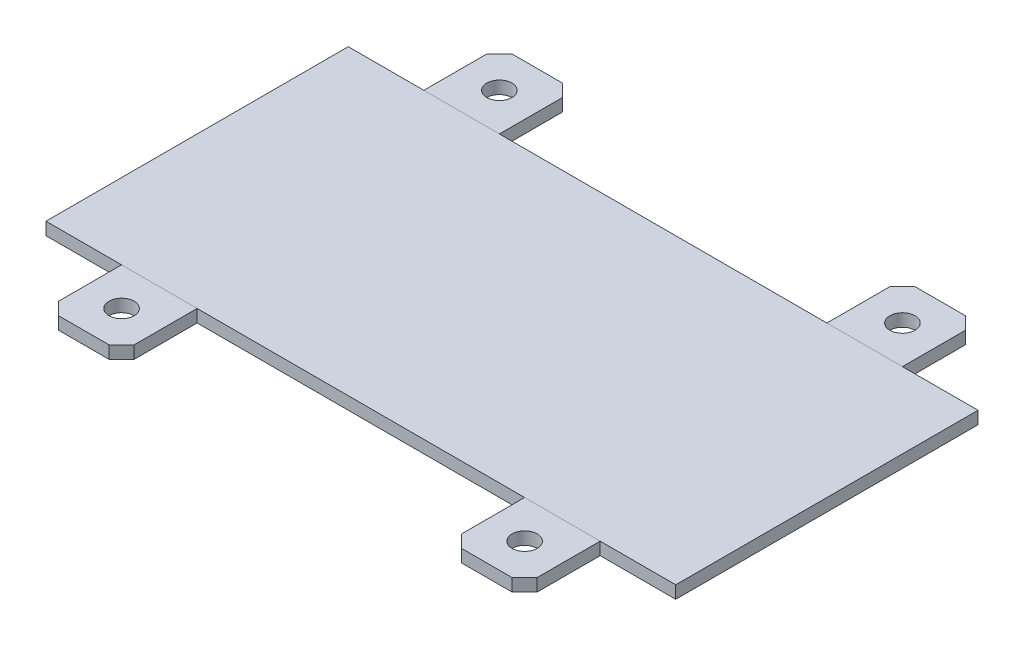
SolidWorks part; units mm, degrees
material "Сталь 3 ГОСТ 535-88"
ref_plane "Спереди" through (0, 0, 0) normal (0, 0, 1) x (1, 0, 0)
ref_plane "Сверху" through (0, 0, 0) normal (0, 1, 0) x (1, 0, 0)
ref_plane "Справа" through (0, 0, 0) normal (1, 0, 0) x (0, 0, -1)
sketch "Эскиз1" plane through (0, 0, 0) normal (0, 1, 0) x (1, 0, 0)
  line L1 (-125, 60) -> (125, 60)
  line L2 (-125, 60) -> (-125, -60)
  line L3 (-125, -60) -> (125, -60)
  line L4 (125, 60) -> (125, -60)
  line L5 (0, -60) -> (0, 60) construction
  line L6 (-125, 0) -> (125, 0) construction
  point P0 (0, 0)
  dimension "D1" = 120
  dimension "D2" = 250
extrude "Бобышка-Вытянуть1" add sketch "Эскиз1" along normal blind 5
sketch "Эскиз2" plane through (0, 0, 0) normal (0, 1, 0) x (1, 0, 0)
  line L0 (125, 60) -> (-125, 60) construction
  line L1 (-95, 60) -> (-65, 60)
  line L2 (-95, 60) -> (-95, 90)
  line L3 (-95, 90) -> (-65, 90)
  line L4 (-65, 60) -> (-65, 90)
  line L5 (-125, 60) -> (-125, -60) construction
  line L6 (-80, 90) -> (-80, 60) construction
  circle A0 centre (-80, 75) radius 5
  dimension "D4" = 10
  dimension "D1" = 30
  dimension "D2" = 30
  dimension "D3" = 30
extrude "Бобышка-Вытянуть2" add sketch "Эскиз2" along normal up to surface (5 mm away) separate body up to face at (0, 5, 0)
chamfer "Фаска1" distance 5 angle 45 2 edges at (-65, 2.5, -90) (-95, 2.5, -90)
mirror "Зеркальное отражение1" about plane through (0, 0, 0) normal (1, 0, 0) of bodies 112
mirror "Зеркальное отражение3" about plane through (0, 0, 0) normal (0, 0, 1) of bodies 112 113
